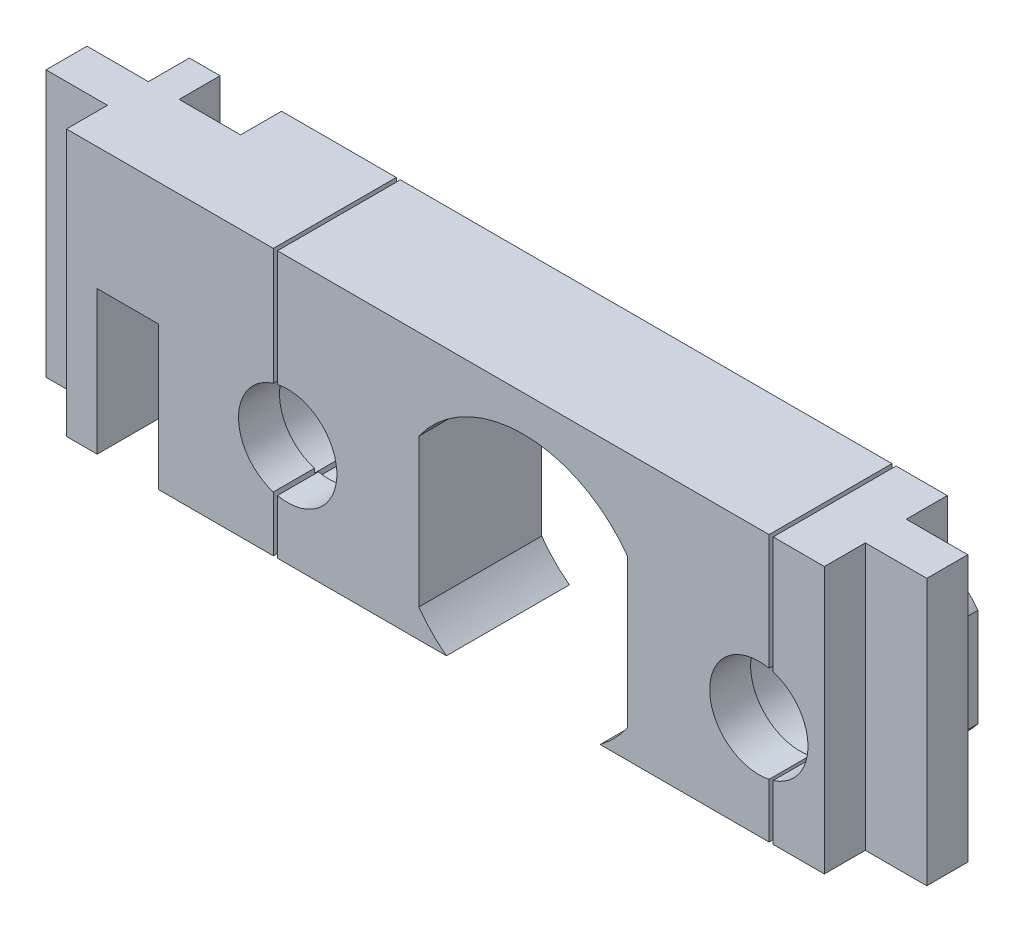
SolidWorks part; units mm, degrees
note: The reader was unsure of these and kept them because the rebuilt part matched: shared geometry of "Sketch17<2>".
ref_plane "Front Plane" through (0, 0, 0) normal (0, 0, 1) x (1, 0, 0)
ref_plane "Top Plane" through (0, 0, 0) normal (0, 1, 0) x (1, 0, 0)
ref_plane "Right Plane" through (0, 0, 0) normal (1, 0, 0) x (0, 0, -1)
sketch "Sketch1" plane through (0, 0, 0) normal (0, 0, 1) x (1, 0, 0)
  line L0 (-11.5, 0) -> (11.5, 0) construction
  line L1 (3.75, -5) -> (14.7, -5)
  line L2 (-14.7, -5) -> (-3.75, -5)
  line L3 (-14.7, -5) -> (-14.7, 8)
  line L4 (-14.7, 8) -> (14.7, 8)
  line L5 (14.7, -5) -> (14.7, 8)
  line L6 (-17.6832, -10.5909) -> (24.7009, -10.5909)
  line L7 (-24.9768, -7) -> (25.0232, -7) construction
  line L8 (-24.9768, -7) -> (-24.9768, -5) construction
  line L9 (-24.9768, -5) -> (-3.75, -5) construction
  line L10 (25.0232, -7) -> (25.0232, -5) construction
  line L11 (-24.9768, -7) -> (25.0232, -5) construction
  line L12 (-24.9768, -5) -> (25.0232, -7) construction
  line L13 (-5.1, -3.6128) -> (-5.1, 3.6128)
  line L14 (9, -3) -> (14, -3) construction
  line L15 (9, -3) -> (9, 3) construction
  line L16 (9, 3) -> (14, 3) construction
  line L17 (14, -3) -> (14, 3) construction
  line L18 (9, -3) -> (14, 3) construction
  line L19 (9, 3) -> (14, -3) construction
  line L20 (5.1, -3.6128) -> (5.1, 3.6128)
  line L21 (-5.1, -3.6128) -> (5.1, 3.6128) construction
  line L22 (-5.1, 3.6128) -> (5.1, -3.6128) construction
  line L23 (3.75, -5) -> (25.0232, -5) construction
  circle A0 centre (0, 0) radius 2 construction
  circle A1 centre (11.5, 0) radius 9.5 construction
  circle A2 centre (-11.5, 0) radius 9.5 construction
  circle A3 centre (11.5, 0) radius 10.5909 construction
  circle A4 centre (-11.5, 0) radius 10.5909 construction
  circle A5 centre (0, 0) radius 0.5
  circle A6 centre (-11.5, 0) radius 1
  circle A7 centre (11.5, 0) radius 1
  arc A8 (5.1, 3.6128) -> (-5.1, 3.6128) centre (0, 0) ccw
  arc A9 (-5.1, -3.6128) -> (-3.75, -5) centre (0, 0) ccw
  arc A10 (3.75, -5) -> (5.1, -3.6128) centre (0, 0) ccw
  point P13 (0, 0)
  point P17 (0, 8)
  point P18 (0.0232, -6)
  point P29 (3.5089, -10.5909)
  dimension "D1" = 4
  dimension "D2" = 19
  dimension "D5" = 1
  dimension "D6" = 2
  dimension "D9" = 12.5
  dimension "D3" = 13
  dimension "D4" = 2
  dimension "D7" = 5
  dimension "D8" = 6
  dimension "D10" = 10.2
  dimension "D11" = 8
  dimension "D12" = 3.2
extrude "Boss-Extrude1" add sketch "Sketch1" along normal blind 6 contours A10 L1 L5 L4 L3 L2 A9 L13 A8 L20 A7 A6
sketch "Sketch2" plane through (0, 0, 0) normal (0, 0, 1) x (1, 0, 0)
  circle A0 centre (-11.5, 0) radius 2.6
  circle A1 centre (11.5, 0) radius 2.6
  dimension "D1" = 5.2
extrude "Cut-Extrude1" cut sketch "Sketch2" along normal blind 6
sketch "Sketch3" plane through (0, 0, 0) normal (0, 0, 1) x (1, 0, 0)
  line L0 (-14.7, -5) -> (-3.75, -5) construction
  line L1 (-14.7, 8) -> (-22.3, 8)
  line L2 (-14.7, 8) -> (-14.7, -5)
  line L3 (-14.7, -5) -> (-22.3, -5)
  line L4 (-22.3, 8) -> (-22.3, -5)
  dimension "D1" = 7.6
extrude "Boss-Extrude2" add sketch "Sketch3" along normal blind 6
sketch "Sketch6" plane through (0, 0, 0) normal (0, 1, 0) x (1, 0, 0)
  line L0 (-22.3, -6) -> (-22.3, 0) construction
  line L1 (-22.3, -2) -> (-25.3, -2)
  line L2 (-22.3, -2) -> (-22.3, -4)
  line L3 (-22.3, -4) -> (-25.3, -4)
  line L4 (-25.3, -2) -> (-25.3, -4)
  line L5 (14.7, -6) -> (14.7, 0) construction
  line L6 (14.7, -2) -> (17.7, -2)
  line L7 (14.7, -2) -> (14.7, -4)
  line L8 (14.7, -4) -> (17.7, -4)
  line L9 (17.7, -2) -> (17.7, -4)
  point P12 (-22.3, -3)
  point P13 (-22.3, -3)
  dimension "D1" = 2
  dimension "D2" = 3
extrude "Boss-Extrude5" add sketch "Sketch6" along normal up to surface (13 mm away) from surface
sketch "Sketch10" plane through (0, 0, 6) normal (0, 0, 1) x (1, 0, 0)
  line L0 (14.7, 2.4) -> (14.7, -2.4)
  line L2 (14.7, -5) -> (14.7, 8) construction
  circle A0 centre (-11.5, 0) radius 2.6
  circle A1 centre (11.5, 0) radius 2.6
  circle A2 centre (-11.5, 0) radius 2.6 construction
  circle A3 centre (11.5, 0) radius 2.6 construction
  arc A4 (14.7, 2.4) -> (14.7, -2.4) centre (11.5, 0) ccw
  circle A5 centre (-11.5, 0) radius 4
  dimension "D1" = 8
extrude "Boss-Extrude6" add sketch "Sketch10" against normal blind 1.5 from surface at -6 starting at face at (-8.9, 0, 0)
sketch "Sketch12" plane through (0, 0, 0) normal (0, 0, -1) x (-1, 0, 0)
  circle A0 centre (-11.5, 0) radius 2.4
  circle A1 centre (11.5, 0) radius 2.4
  circle A2 centre (11.5, 0) radius 2.6
  circle A3 centre (-11.5, 0) radius 2.6
  circle A4 centre (-11.5, 0) radius 2.6 construction
  circle A5 centre (11.5, 0) radius 2.6 construction
  dimension "D1" = 4.8
extrude "Boss-Extrude7" add sketch "Sketch12" along normal blind 2 from surface at -6 starting at face at (-8.9, 0, 6)
sketch "Sketch13" plane through (0, -5, 0) normal (0, -1, 0) x (1, 0, 0)
  line L12 (-22.3, 6) -> (-3.75, 6) construction
  line L13 (-22.3, 0) -> (-16.3, 0)
  line L14 (-22.3, 0) -> (-22.3, 2)
  line L15 (-22.3, 2) -> (-20.8, 2)
  line L16 (-16.3, 0) -> (-16.3, 2)
  line L18 (-20.8, 2) -> (-20.8, 6)
  line L19 (-20.8, 6) -> (-17.8, 6)
  line L20 (-17.8, 2) -> (-17.8, 6)
  line L21 (-17.8, 2) -> (-16.3, 2)
  dimension "D1" = 6
  dimension "D2" = 3
  dimension "D3" = 2
extrude "Cut-Extrude2" cut sketch "Sketch13" against normal blind 7
sketch "Sketch14" plane through (0, 0, 0) normal (0, 0, -1) x (-1, 0, 0)
  line L0 (22.3, 8) -> (-14.7, 8) construction
  line L1 (20.8, 2) -> (17.8, 2)
  line L2 (20.8, 2) -> (20.8, 8)
  line L3 (20.8, 8) -> (17.8, 8)
  line L4 (17.8, 2) -> (17.8, 8)
  line L5 (17.8, 2) -> (17.8, -5) construction
extrude "Cut-Extrude3" cut sketch "Sketch14" against normal blind 2
sketch "Sketch15" plane through (0, 0, 0) normal (0, 0, 1) x (1, 0, 0)
  line L0 (-17.8, 8) -> (14.7, 8) construction
  line L1 (-12, -5) -> (-12.2, -5)
  line L2 (-12, -5) -> (-12, 8)
  line L3 (-12, 8) -> (-12.2, 8)
  line L4 (-12.2, -5) -> (-12.2, 8)
  line L5 (-12, -5) -> (-12.2, 8) construction
  line L6 (-12, 8) -> (-12.2, -5) construction
  line L7 (3.75, -5) -> (14.7, -5) construction
  line L8 (12, -5) -> (12.2, -5)
  line L9 (12, -5) -> (12, 8)
  line L10 (12, 8) -> (12.2, 8)
  line L11 (12.2, -5) -> (12.2, 8)
  line L12 (12, -5) -> (12.2, 8) construction
  line L13 (12, 8) -> (12.2, -5) construction
  circle A0 centre (-11.5, 0) radius 2.4 construction
  circle A1 centre (11.5, 0) radius 2.4 construction
  point P0 (-12.1, 1.5)
  point P7 (12.1, 1.5)
  dimension "D1" = 0.2
  dimension "D2" = 0.5
  dimension "D3" = 0.5
extrude "Cut-Extrude5" cut sketch "Sketch15" against normal mid plane 15
sketch "Sketch16" plane through (12, 0, 0) normal (1, 0, 0) x (0, 0, -1)
  line L0 (0, 8) -> (-6, 2.3473) construction
  line L2 (-1.5, 3.6737) -> (-4.5, 3.6737)
  line L3 (-1.5, 3.6737) -> (-1.5, 6.6737)
  line L4 (-1.5, 6.6737) -> (-4.5, 6.6737)
  line L5 (-4.5, 3.6737) -> (-4.5, 6.6737)
  line L6 (-1.5, 3.6737) -> (-4.5, 6.6737) construction
  line L7 (-1.5, 6.6737) -> (-4.5, 3.6737) construction
  point P4 (-3, 5.1737)
  dimension "D1" = 3
extrude "Cut-Extrude6" cut sketch "Sketch16" against normal blind 3
mirror "Mirror1" about plane through (0, 0, 0) normal (1, 0, 0) of "Cut-Extrude6"
sketch "Sketch17" plane through (-12.2, 0, 0) normal (1, 0, 0) x (0, 0, -1)
  line L0 (-4.5, 6.6737) -> (-1.5, 3.6737) construction
  line L2 (-4.4, 3.7737) -> (-1.6, 3.7737)
  line L3 (-4.4, 3.7737) -> (-4.4, 6.5737)
  line L4 (-4.4, 6.5737) -> (-1.6, 6.5737)
  line L5 (-1.6, 3.7737) -> (-1.6, 6.5737)
  line L6 (-4.4, 3.7737) -> (-1.6, 6.5737) construction
  line L7 (-4.4, 6.5737) -> (-1.6, 3.7737) construction
  point P4 (-3, 5.1737)
  dimension "D1" = 2.8
extrude "Boss-Extrude9" add sketch "Sketch17" along normal blind 3
extrude "Boss-Extrude10" add sketch "Sketch17<2>" against normal blind 3 from surface at 24.4 starting at face at (12.2, 4.1845, 2.125)
sketch "Sketch17<2>" plane through (-12.2, 0, 0) normal (1, 0, 0) x (0, 0, -1) same geometry as "Sketch17"
